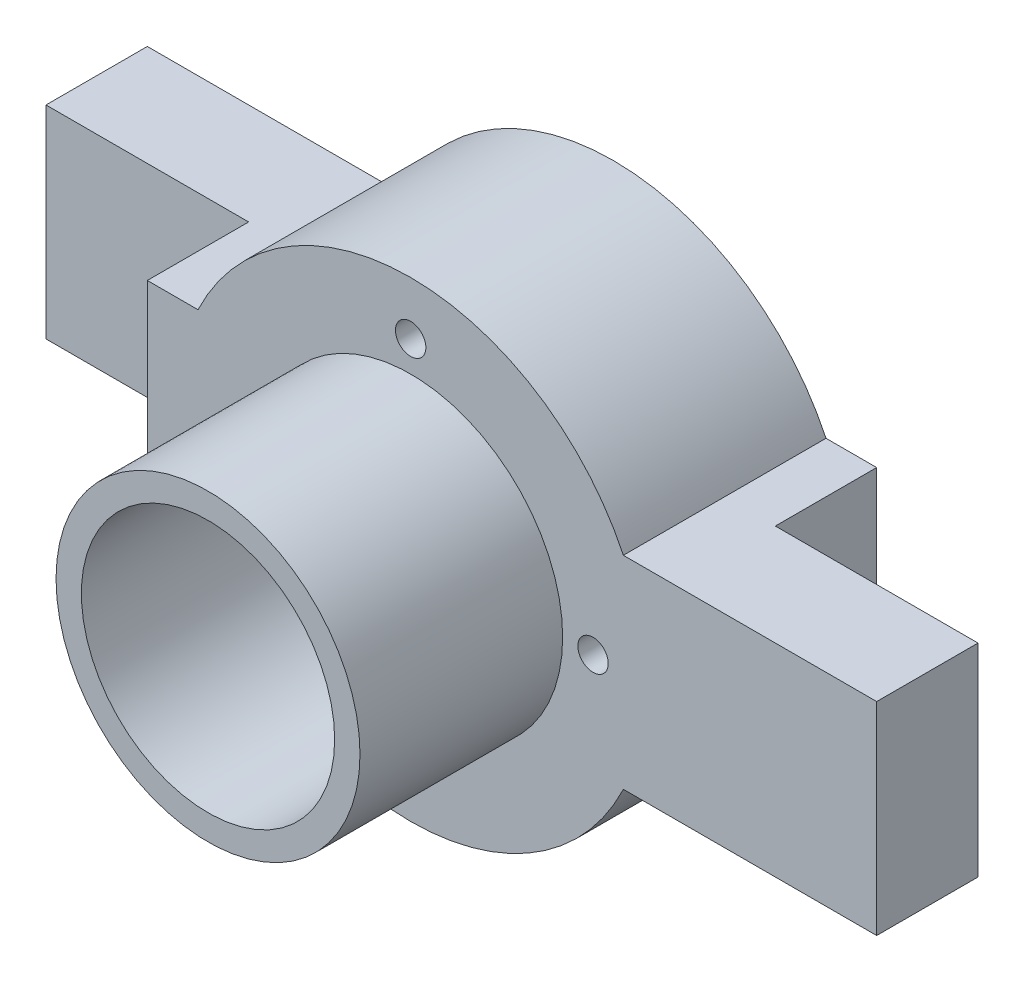
SolidWorks part; units mm, degrees
ref_plane "Alzado" through (0, 0, 0) normal (0, 0, 1) x (1, 0, 0)
ref_plane "Planta" through (0, 0, 0) normal (0, 1, 0) x (1, 0, 0)
ref_plane "Vista lateral" through (0, 0, 0) normal (1, 0, 0) x (0, 0, -1)
sketch "Croquis1" plane through (0, 0, 0) normal (0, 0, 1) x (1, 0, 0)
  circle A0 centre (0, 0) radius 15
  circle A1 centre (0, 0) radius 12.5
  dimension "D1" = 30
  dimension "D2" = 25
extrude "Saliente-Extruir1" add sketch "Croquis1" against normal blind 20
sketch3d "Croquis3D3"
  line L0 (0, 0, 0) -> (0, 0, -60) construction
  line L1 (0, 0, -60) -> (40, 0, -60) construction
  line L2 (40, 0, -60) -> (40, 0, -35) construction
  line L3 (40, 0, -35) -> (0, 0, -35) construction
  line L4 (0, 0, -35) -> (-40, 0, -35) construction
  line L5 (-40, 0, -35) -> (-40, 0, -60.0108) construction
  line L6 (-40, 0, -60.0108) -> (0, 0, -60) construction
  line L7 (0, 0, -35) -> (-46.9846, -17.101, -35) construction
  line L8 (0, 0, -35) -> (46.9846, -17.101, -35) construction
  line L9 (0, 0, 0) -> (0, -10.0221, 0) construction
  line L10 (46.9846, -17.101, -35) -> (46.9846, 0, -35) construction
  line L11 (-46.9846, -17.101, -35) -> (-46.9846, 0, -35) construction
  dimension "D2" = 25
  dimension "D1" = 60
  dimension "D3" = 40
  dimension "D4" = 140
  dimension "D5" = 50
sketch "Croquis8" plane through (0, 0, -20) normal (0, 0, -1) x (-1, 0, 0)
  line L0 (0, 0) -> (0, 18) construction
  line L1 (0, 0) -> (-18, 0) construction
  line L2 (0, 0) -> (-40, 0) construction
  line L3 (0, 0) -> (0, -18) construction
  line L4 (0, 0) -> (18, 0) construction
  line L5 (0, 0) -> (40, 0) construction
  circle A0 centre (0, 0) radius 23.25
  circle A1 centre (0, 18) radius 1.5
  circle A2 centre (18, 0) radius 1.5
  circle A3 centre (0, -18) radius 1.5
  circle A4 centre (-18, 0) radius 1.5
  dimension "D1" = 46.5
  dimension "D3" = 3
  dimension "D2" = 18
extrude "Saliente-Extruir2" add sketch "Croquis8" along normal blind 20
sketch "Croquis10" plane through (0, 0, -40) normal (0, 0, -1) x (-1, 0, 0)
  line L0 (20.9896, 0) -> (-20.9896, 0) construction
  line L1 (-20.9896, 10) -> (-20.9896, -10) construction
  line L2 (-20.9896, 10) -> (-45.9896, 10)
  line L3 (-45.9896, 10) -> (-45.9896, -10)
  line L4 (-45.9896, -10) -> (-20.9896, -10)
  line L5 (-20.9896, -10) -> (-20.9896, 10)
  line L6 (0, 0) -> (0, 10) construction
  line L7 (45.9896, -10) -> (20.9896, -10)
  line L8 (45.9896, 10) -> (45.9896, -10)
  line L9 (20.9896, 10) -> (45.9896, 10)
  line L10 (20.9896, -10) -> (20.9896, 10)
  circle A0 centre (0, 0) radius 23.25 construction
  point P5 (0, 0)
  point P11 (-20.9896, 0)
  dimension "D1" = 20
  dimension "D2" = 25
extrude "Saliente-Extruir6" add sketch "Croquis10" against normal blind 20
sketch "Croquis11" plane through (0, 0, -20) normal (0, 0, -1) x (-1, 0, 0)
  line L6 (0, 0) -> (0, 8.6178) construction
  line L7 (25.9896, -10) -> (45.9896, -10)
  line L8 (25.9896, 10) -> (25.9896, -10)
  line L9 (45.9896, 10) -> (25.9896, 10)
  line L10 (45.9896, -10) -> (45.9896, 10)
extrude "Cortar-Extruir2" cut sketch "Croquis11" along normal blind 10
sketch "Croquis12" plane through (0, 0, -40) normal (0, 0, 1) x (1, 0, 0)
  line L0 (45.9896, 10) -> (25.9896, 10)
  line L1 (20.9896, 10) -> (45.9896, 10) construction
  line L2 (25.9896, 10) -> (25.9896, -10)
  line L3 (45.9896, -10) -> (20.9896, -10) construction
  line L4 (25.9896, -10) -> (45.9896, -10)
  line L5 (45.9896, -10) -> (45.9896, 10)
  dimension "D1" = 20
extrude "Cortar-Extruir3" cut sketch "Croquis12" along normal blind 10
